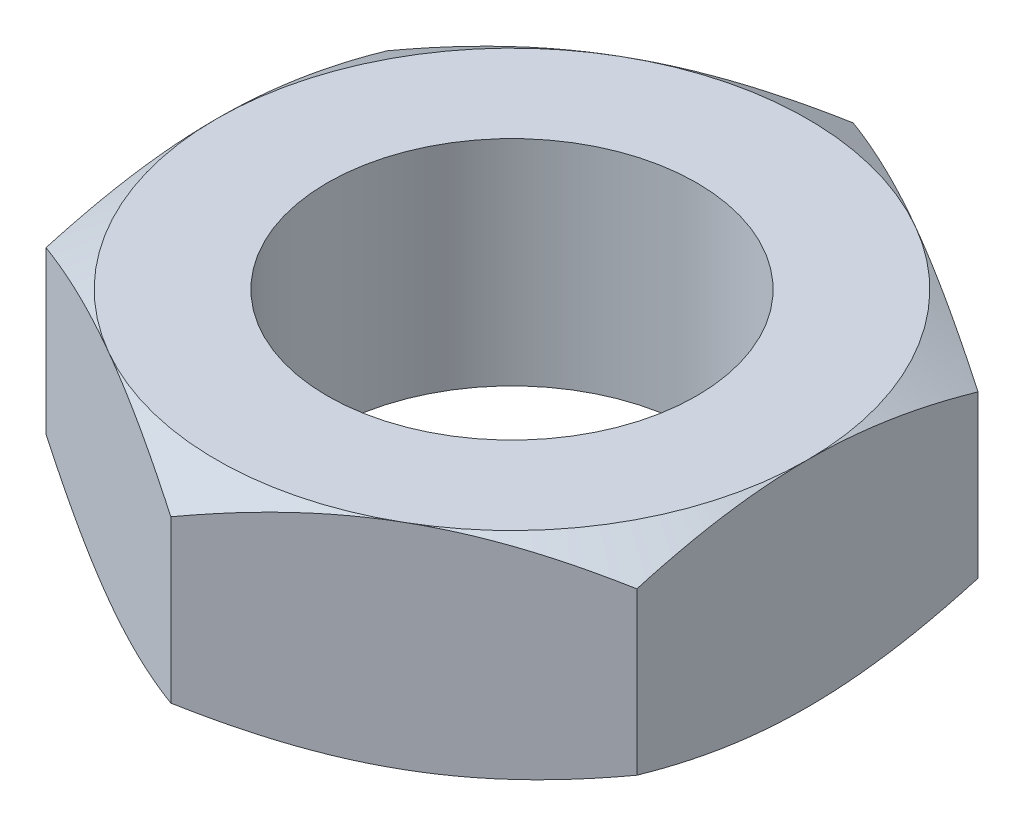
SolidWorks part; units mm, degrees
ref_plane "Front Plane" through (0, 0, 0) normal (0, 0, 1) x (1, 0, 0)
ref_plane "Top Plane" through (0, 0, 0) normal (0, 1, 0) x (1, 0, 0)
ref_plane "Right Plane" through (0, 0, 0) normal (1, 0, 0) x (0, 0, -1)
sketch "Sketch1" plane through (0, 0, 0) normal (0, 1, 0) x (1, 0, 0)
  line L1 (-4, 2.3094) -> (-4, -2.3094)
  line L2 (-4, -2.3094) -> (0, -4.6188)
  line L3 (0, -4.6188) -> (4, -2.3094)
  line L4 (4, -2.3094) -> (4, 2.3094)
  line L5 (4, 2.3094) -> (0, 4.6188)
  line L6 (0, 4.6188) -> (-4, 2.3094)
  circle A0 centre (0, 0) radius 4 construction
  circle A1 centre (0, 0) radius 2.5
  dimension "Thread Size" = 5
  dimension "Hex" = 8
extrude "Boss-Extrude1" add sketch "Sketch1" along normal mid plane 2.9
sketch "Sketch2" plane through (0, 1.45, 0) normal (0, 1, 0) x (1, 0, 0)
  circle A0 centre (0, 0) radius 2.5 construction
  circle A1 centre (0, 0) radius 2.5
curve "Helix/Spiral1" pitch 0.8 height 3.7 turns 4.625 parameters "Pitch"=0.8
sketch "Sketch5" plane through (0, 1.45, 0) normal (0, 1, 0) x (1, 0, 0)
  circle A0 centre (0, 0) radius 4 construction
  circle A1 centre (0, 0) radius 4
extrude "Cut-Extrude2" cut sketch "Sketch5" against normal through all draft 60 flip side to cut
mirror "Mirror1" about plane through (0, 0, 0) normal (0, 1, 0) of "Cut-Extrude2"
sketch "Sketch3" [suppressed] plane through (0, 0, 0) normal (1, 0, 0) x (0, 0, -1)
  line L0 (1.9804, 2.4) -> (2.5, 2.7)
  line L1 (2.5, 2.7) -> (2.5, 2)
  line L2 (2.5, 2) -> (1.9804, 2.3)
  line L3 (1.9804, 2.3) -> (1.9804, 2.4)
  line L4 (2.2402, 2.55) -> (2.2402, 2.15) construction
  line L5 (1.9804, 2.35) -> (2.5, 2.35) construction
  line L6 (2.5, 2) -> (-2.5, 2) construction
  dimension "D1" = 60
  dimension "D2" = 0.1
sweep "Sweep1" [suppressed] add profiles "Sketch3" path "Helix/Spiral1"
sketch "Sketch4" [suppressed] plane through (0, 2, 0) normal (0, 1, 0) x (1, 0, 0)
  circle A1 centre (0, 0) radius 2.5
  circle A2 centre (0, 0) radius 2.5
  dimension "D1" = 0
extrude "Cut-Extrude1" [suppressed] cut sketch "Sketch4" along normal through all and the other way through all draft 45
sketch "Sketch8" [suppressed] plane through (0, -2, 0) normal (0, -1, 0) x (1, 0, 0)
  circle A0 centre (0, 0) radius 2.5
  arc A1 (0, -2.5) -> (-1.7678, -1.7678) centre (0, 0) ccw construction
extrude "Cut-Extrude3" [suppressed] cut sketch "Sketch8" along normal through all and the other way through all draft 45
equation "\"D2@Sketch3\" = \"Pitch@Helix/Spiral1\"*.125"
equation "\"D3@Sketch3\" = \"Pitch@Helix/Spiral1\"*.5"
equation "\"D3@Helix/Spiral1\" = \"Height@Boss-Extrude1\"+\"Pitch@Helix/Spiral1\""
